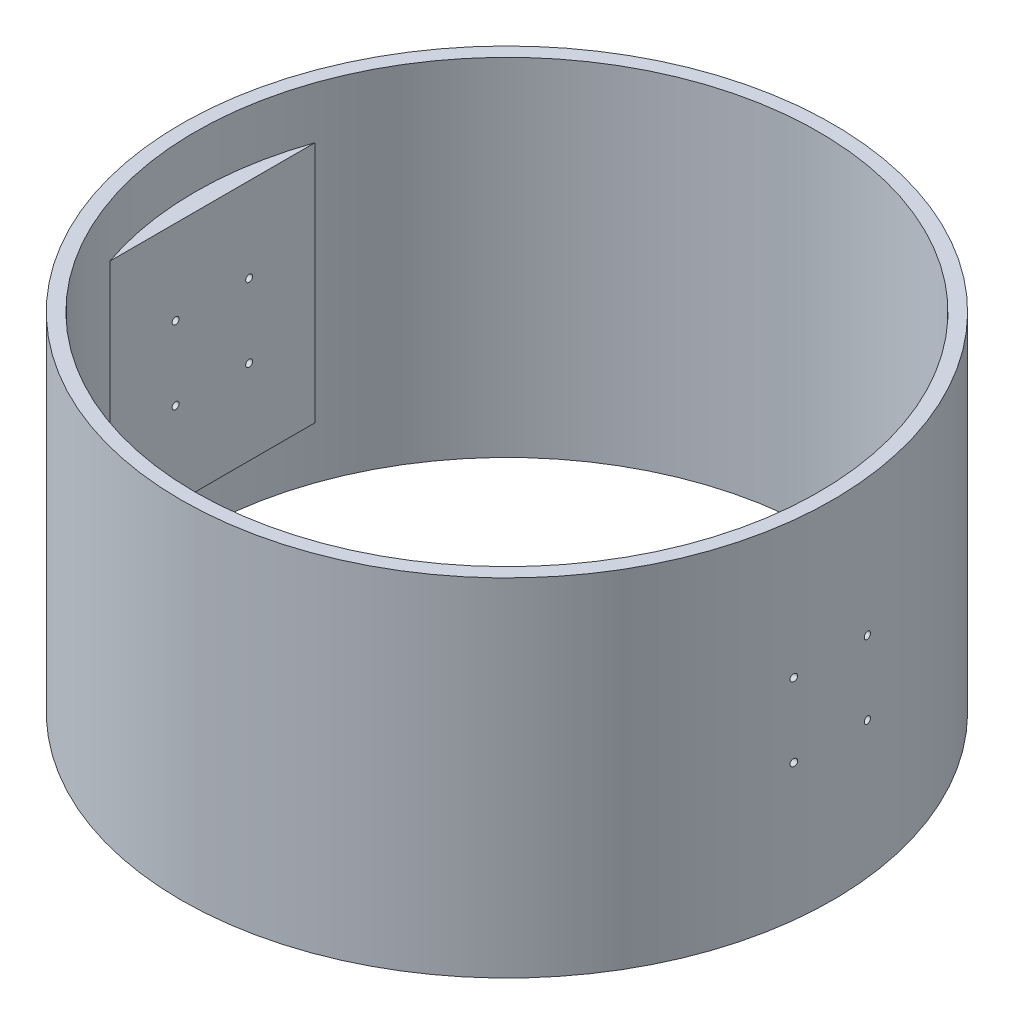
SolidWorks part; units mm, degrees
ref_plane "Front Plane" through (0, 0, 0) normal (0, 0, 1) x (1, 0, 0)
ref_plane "Top Plane" through (0, 0, 0) normal (0, 1, 0) x (1, 0, 0)
ref_plane "Right Plane" through (0, 0, 0) normal (1, 0, 0) x (0, 0, -1)
sketch "Sketch1" plane through (0, 0, 0) normal (0, 1, 0) x (1, 0, 0)
  circle A0 centre (0, 0) radius 90
  circle A1 centre (0, 0) radius 94
  dimension "D1" = 4
  dimension "D2" = 180
extrude "Boss-Extrude1" add sketch "Sketch1" along normal mid plane 100
sketch "Sketch2" plane through (0, 0, 0) normal (1, 0, 0) x (0, 0, -1)
  line L0 (-10.6066, 10.6066) -> (10.6066, -10.6066) construction
  line L1 (-35, -35) -> (35, -35)
  line L2 (-35, -35) -> (-35, 35)
  line L3 (-35, 35) -> (35, 35)
  line L4 (35, -35) -> (35, 35)
  line L5 (-35, -35) -> (35, 35) construction
  line L6 (-35, 35) -> (35, -35) construction
  line L7 (-10.6066, -10.6066) -> (10.6066, 10.6066) construction
  circle A4 centre (10.6066, 10.6066) radius 1
  circle A5 centre (0, 0) radius 15 construction
  circle A6 centre (-10.6066, 10.6066) radius 1
  circle A7 centre (-10.6066, -10.6066) radius 1
  circle A8 centre (10.6066, -10.6066) radius 1
  point P0 (0, 0)
  point P16 (0, 0)
  point P17 (0, 0)
  point P18 (0, 0)
  point P19 (-9.6169, 11.5115)
  point P20 (0, 0)
  dimension "D3" = 15
  dimension "D2" = 2
  dimension "D1" = 70
  dimension "D5" = 70
  dimension "D6" = 90
  dimension "D7" = 45
extrude "Boss-Extrude2" add sketch "Sketch2" against normal up to surface and the other way up to surface contours L2 L1 L4 L3 up to face at (0, 50, 90) other way up to face at (0, 50, 90)
sketch "Sketch3" plane through (0, 0, 0) normal (0, 1, 0) x (1, 0, 0)
  line L2 (-85, 29.5804) -> (-85, -29.5804)
  line L4 (85, 29.5804) -> (85, -29.5804)
  line L6 (-85, 29.5804) -> (85, 29.5804) construction
  line L7 (-85, -29.5804) -> (85, -29.5804) construction
  circle A0 centre (0, 0) radius 90 construction
  arc A1 (-85, -29.5804) -> (85, -29.5804) centre (0, 0) ccw
  arc A2 (85, 29.5804) -> (-85, 29.5804) centre (0, 0) ccw
  point P4 (85.2789, -28.7666)
  dimension "D1" = 170
extrude "Cut-Extrude1" cut sketch "Sketch3" against normal through all both and the other way through all
extrude "Cut-Extrude3" cut sketch "Sketch2<3>" against normal through all both and the other way through all contours A4 | A6 | A7 | A8 region at (0, 10.6066, -10.6066) region at (0, 10.6066, 10.6066) region at (0, -10.6066, 10.6066) region at (0, -10.6066, -10.6066)
sketch "Sketch2<3>" plane through (0, 0, 0) normal (1, 0, 0) x (0, 0, -1) same geometry as "Sketch2"
